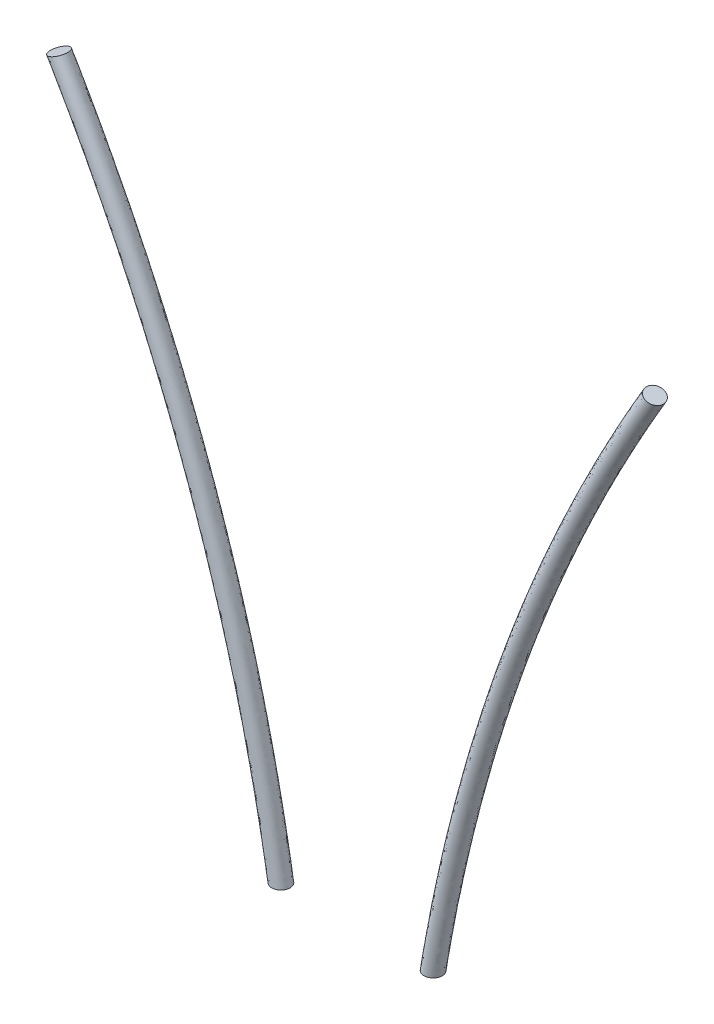
SolidWorks part; units mm, degrees
material "Rubber"
ref_plane "Front Plane" through (0, 0, 0) normal (0, 0, 1) x (1, 0, 0)
ref_plane "Top Plane" through (0, 0, 0) normal (0, 1, 0) x (1, 0, 0)
ref_plane "Right Plane" through (0, 0, 0) normal (1, 0, 0) x (0, 0, -1)
sketch "Sketch1" plane through (0, 0, 0) normal (0, 0, 1) x (1, 0, 0)
  line L0 (0, 43.6117) -> (0, -32.2629) construction
  line L1 (12.5, -77.1506) -> (-12.5, -77.1506) construction
  spline S0 degree 2 poles (12.5, -77.1506) (21.4316, -23.856) (48.922, 22.8494) knots 0 0 0 1 1 1
  spline S1 degree 2 poles (-12.5, -77.1506) (-21.4316, -23.856) (-48.922, 22.8494) knots 0 0 0 1 1 1
  point P9 (-34.0832, -57.2541)
  point P10 (-69.0421, 18.6866)
  point P11 (-24.507, -29.9094)
  point P12 (-48.922, 22.8494)
  dimension "D1" = 25
  dimension "D2" = 100
ref_plane "Plane3" through (0, -77.1506, 0) normal (0, 1, 0) x (1, 0, 0)
sketch "Sketch2" plane through (0, -77.1506, 0) normal (0, 1, 0) x (1, 0, 0)
  line L1 (0, -8.4432) -> (0, 14.3372) construction
  line L3 (12.5, 0) -> (-12.5, 0) construction
  circle A0 centre (12.5, 0) radius 1.5
  point P2 (15, 0)
  point P9 (13.1086, 0)
  point P10 (15.6194, 0)
  point P11 (12.8348, 0)
  point P13 (16.0663, 0)
  point P15 (0, 0)
  dimension "D1" = 3
sweep "Sweep1" add profiles "Sketch2" path "Sketch1"
mirror "Mirror4" about plane through (0, 0, 0) normal (1, 0, 0) of bodies 101
